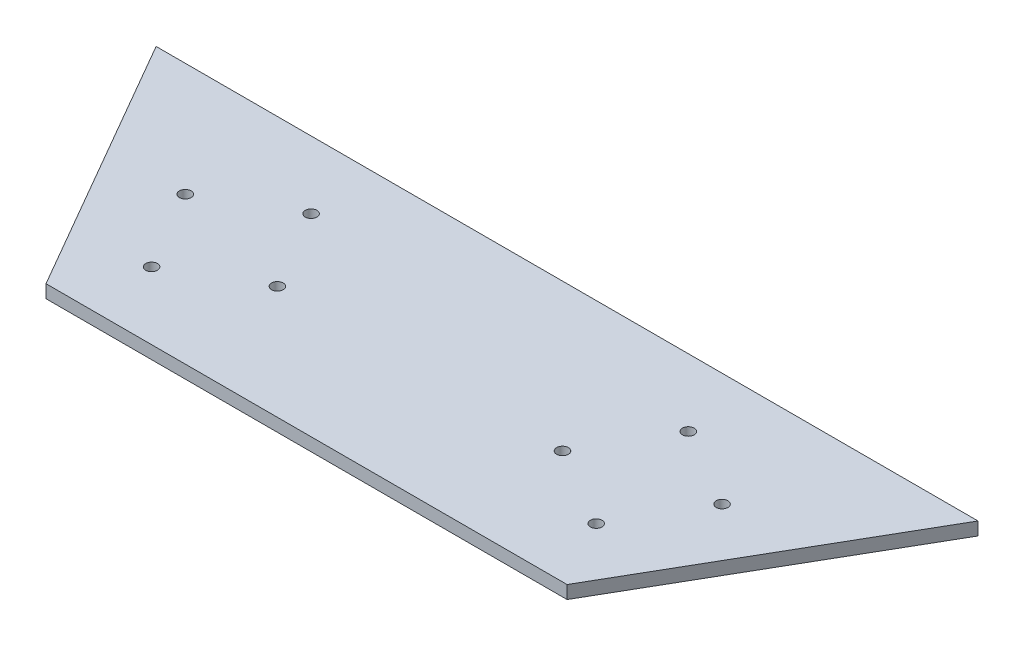
SolidWorks part; units mm, degrees
ref_plane "Front Plane" through (0, 0, 0) normal (0, 0, 1) x (1, 0, 0)
ref_plane "Top Plane" through (0, 0, 0) normal (0, 1, 0) x (1, 0, 0)
ref_plane "Right Plane" through (0, 0, 0) normal (1, 0, 0) x (0, 0, -1)
sketch "Sketch1" plane through (0, 0, 0) normal (0, 1, 0) x (1, 0, 0)
  line L0 (-200, 0) -> (200, 0)
  line L1 (200, 0) -> (315.4701, 200)
  line L2 (315.4701, 200) -> (-315.4701, 200)
  line L3 (-315.4701, 200) -> (-200, 0)
  point P4 (0, 0)
  dimension "D1" = 60
  dimension "D2" = 60
  dimension "D3" = 400
  dimension "D4" = 200
extrude "Boss-Extrude1" add sketch "Sketch1" along normal blind 10
sketch "Sketch9" plane through (0, 10, 0) normal (0, 1, 0) x (1, 0, 0)
  line L0 (257.735, 100) -> (-257.735, 100) construction
  line L2 (206.0313, 112.941) -> (170.676, 51.7037) construction
  line L3 (170.676, 51.7037) -> (157.735, 100) construction
  line L4 (157.735, 100) -> (206.0313, 112.941) construction
  line L5 (200, 0) -> (315.4701, 200) construction
  line L6 (-206.0313, 112.941) -> (-170.676, 51.7037) construction
  line L7 (-170.676, 51.7037) -> (-157.735, 100) construction
  line L8 (-157.735, 100) -> (-206.0313, 112.941) construction
  line L9 (-315.4701, 200) -> (-200, 0) construction
  point P2 (0, 0)
  point P3 (0, 0)
  point P14 (0, 0)
  point P18 (0, 0)
  point P19 (0, 0)
  point P20 (0, 0)
  point P21 (0, 0)
  point P22 (158.2305, 90.0581)
  dimension "D1" = 100
  dimension "D2" = 100
  dimension "D3" = 50
  dimension "D5" = 50
hole_wizard "M8 Clearance Hole4" positions "Sketch12" profile "Sketch13" hole size "M8" standard "ISO" end condition through all
sketch "Sketch12" plane through (0, 10, 0) normal (0, 1, 0) x (1, 0, 0)
  point P0 (-170.676, 51.7037)
sketch "Sketch13" plane through (-170.676, 10, -51.7037) normal (1, 0, 0) x (0, 0, 1)
  line L0 (0, 0) -> (0, 10)
  line L1 (0, 10) -> (4.5, 10)
  line L2 (4.5, 10) -> (4.5, 0)
  line L5 (4.5, 0) -> (0, 0)
  line L11 (0, -6.35) -> (0, 107.95) construction
  dimension "Thru Hole Dia." = 9
  dimension "Thru Hole Depth" = 10
hole_wizard "M8 Clearance Hole5" positions "Sketch14" profile "Sketch15" hole size "M8" standard "ISO" end condition through all
sketch "Sketch14" plane through (0, 10, 0) normal (0, 1, 0) x (1, 0, 0)
  point P0 (170.676, 51.7037)
sketch "Sketch15" plane through (170.676, 10, -51.7037) normal (1, 0, 0) x (0, 0, 1)
  line L0 (0, 0) -> (0, 10)
  line L1 (0, 10) -> (4.5, 10)
  line L2 (4.5, 10) -> (4.5, 0)
  line L5 (4.5, 0) -> (0, 0)
  line L11 (0, -6.35) -> (0, 107.95) construction
  dimension "Thru Hole Dia." = 9
  dimension "Thru Hole Depth" = 10
ref_axis "Axis2" through (157.735, 10, -100) along (0, 1, 0)
ref_axis "Axis3" through (-157.735, 10, -100) along (0, 1, 0)
pattern_circular "CirPattern1" count 4 over 360 about axis through (157.735, 10, -100) along (0, 1, 0) of "M8 Clearance Hole5"
pattern_circular "CirPattern2" count 4 over 360 about axis through (-157.735, 10, -100) along (0, 1, 0) of "M8 Clearance Hole4"
